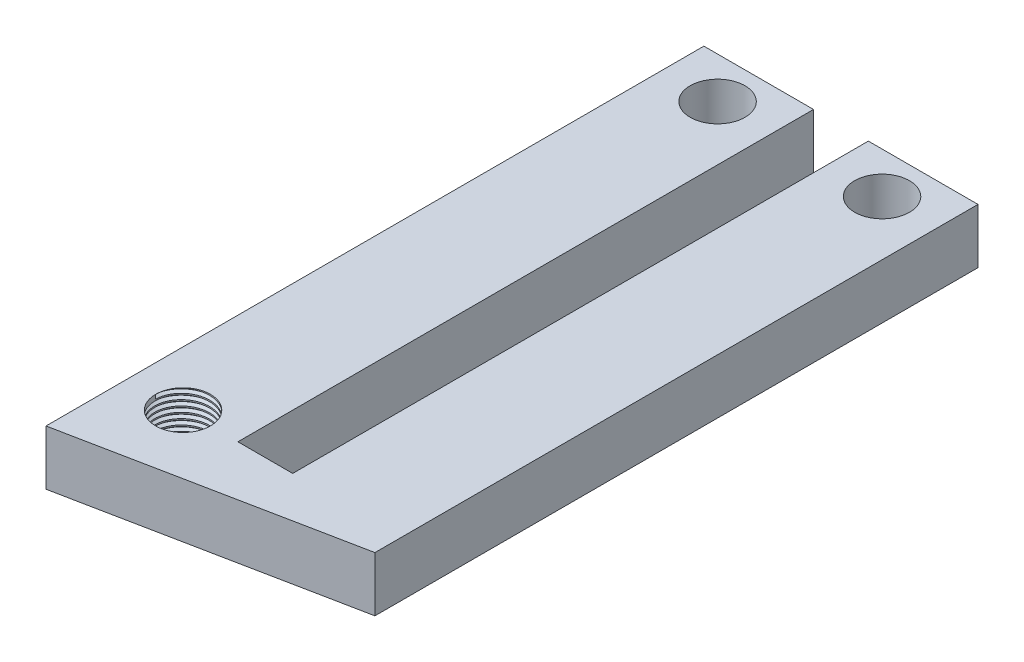
SolidWorks part; units mm, degrees
ref_plane "Front Plane" through (0, 0, 0) normal (0, 0, 1) x (1, 0, 0)
ref_plane "Top Plane" through (0, 0, 0) normal (0, 1, 0) x (1, 0, 0)
ref_plane "Right Plane" through (0, 0, 0) normal (1, 0, 0) x (0, 0, -1)
sketch "Sketch1" plane through (0, 0, 0) normal (0, 0, 1) x (1, 0, 0)
  line L0 (0, 0) -> (0, 12.7)
  line L1 (0, 12.7) -> (25.4, 12.7)
  line L2 (25.4, 12.7) -> (25.4, 0)
  line L3 (25.4, 0) -> (0, 0)
  line L4 (38.1, 12.7) -> (38.1, 0)
  line L5 (38.1, 0) -> (63.5, 0)
  line L6 (63.5, 0) -> (63.5, 12.7)
  line L7 (63.5, 12.7) -> (38.1, 12.7)
  dimension "D1" = 25.4
  dimension "D2" = 12.7
  dimension "D3" = 25.4
  dimension "D4" = 12.7
  dimension "D5" = 12.7
extrude "Boss-Extrude1" add sketch "Sketch1" along normal blind 152.4
sketch "Sketch2" plane through (25.4, 0, 0) normal (1, 0, 0) x (0, 0, -1)
  line L0 (-152.4, 12.7) -> (-152.4, 0)
  line L1 (-152.4, 0) -> (-133.35, 0)
  line L2 (-152.4, 0) -> (0, 0) construction
  line L3 (-133.35, 0) -> (-133.35, 12.7)
  line L4 (-152.4, 12.7) -> (0, 12.7) construction
  line L5 (-133.35, 12.7) -> (-152.4, 12.7)
  dimension "D1" = 19.05
extrude "Boss-Extrude2" add sketch "Sketch2" along normal up to surface (12.7 mm away) up to face at (38.1, 6.35, 76.2)
sketch "Sketch3" plane through (0, 12.7, 0) normal (0, 1, 0) x (1, 0, 0)
  line L0 (12.7, 0) -> (12.7, -19.05) construction
  line L1 (25.4, 0) -> (0, 0) construction
  line L2 (12.7, -19.05) -> (50.8, -19.05) construction
  line L3 (50.8, -19.05) -> (50.8, 0) construction
  line L4 (63.5, 0) -> (38.1, 0) construction
  circle A0 centre (12.7, -9.525) radius 6.35
  circle A1 centre (50.8, -9.525) radius 6.35
  point P8 (12.7, -9.525)
  point P13 (50.8, -9.525)
  dimension "D2" = 12.7
  dimension "D3" = 12.7
  dimension "D1" = 19.05
extrude "Cut-Extrude1" cut sketch "Sketch3" against normal through all
sketch "Sketch4" plane through (0, 12.7, 0) normal (0, 1, 0) x (1, 0, 0)
  line L0 (0, -152.4) -> (63.5, -139.7)
  line L1 (63.5, -152.4) -> (63.5, 0) construction
  line L2 (63.5, -139.7) -> (63.5, -152.4)
  line L3 (63.5, -152.4) -> (0, -152.4)
  dimension "D1" = 12.7
extrude "Cut-Extrude4" cut sketch "Sketch4" against normal up to surface (12.7 mm away) up to face at (12.7, 0, 15.875)
sketch "Sketch5" plane through (0, 12.7, 0) normal (0, 1, 0) x (1, 0, 0)
  line L2 (0, -152.4) -> (0, 0) construction
  line L3 (12.7, 0) -> (12.7, -149.86) construction
  line L4 (25.4, 0) -> (0, 0) construction
  line L5 (63.5, -139.7) -> (0, -152.4) construction
  line L6 (25.4, -133.35) -> (0, -133.35) construction
  line L7 (0, -133.35) -> (0, -152.4) construction
  circle A0 centre (12.7, -133.35) radius 6.35
  dimension "D1" = 12.7
extrude "Cut-Extrude5" cut sketch "Sketch5" against normal up to surface (12.7 mm away) contours A0 up to face at (12.7, 0, 15.875)
thread "Thread1" pitch 1.27 method cut profile "Thread Profile1" start angle 0, offset 0, length 0, pitch 1.27, diameter 12.7
ref_plane "Plane1" through (6.35, 12.7, 133.35) normal (0, 0, 1) x (-1, 0, 0)
sketch "Thread Profile1" plane through (6.35, 12.7, 133.35) normal (0, 0, 1) x (-1, 0, 0)
  line L0 (0, 0) -> (0, 1.27) construction
  line L1 (0, 0) -> (0.6874, 0.3969)
  line L2 (0.6874, 0.3969) -> (0.6874, 0.5556)
  line L3 (0.6874, 0.5556) -> (0, 0.9525)
  line L4 (0.6874, 0.4762) -> (0, 0.4762) construction
  line L11 (0, 0) -> (0, 0.9525)
  point P2 (0, 0)
  dimension "Pitch" = 1.27
  dimension "Profile_Angle" = 60
  dimension "Profile_Land" = 0.1588
  dimension "Profile_Height" = 0.6874
